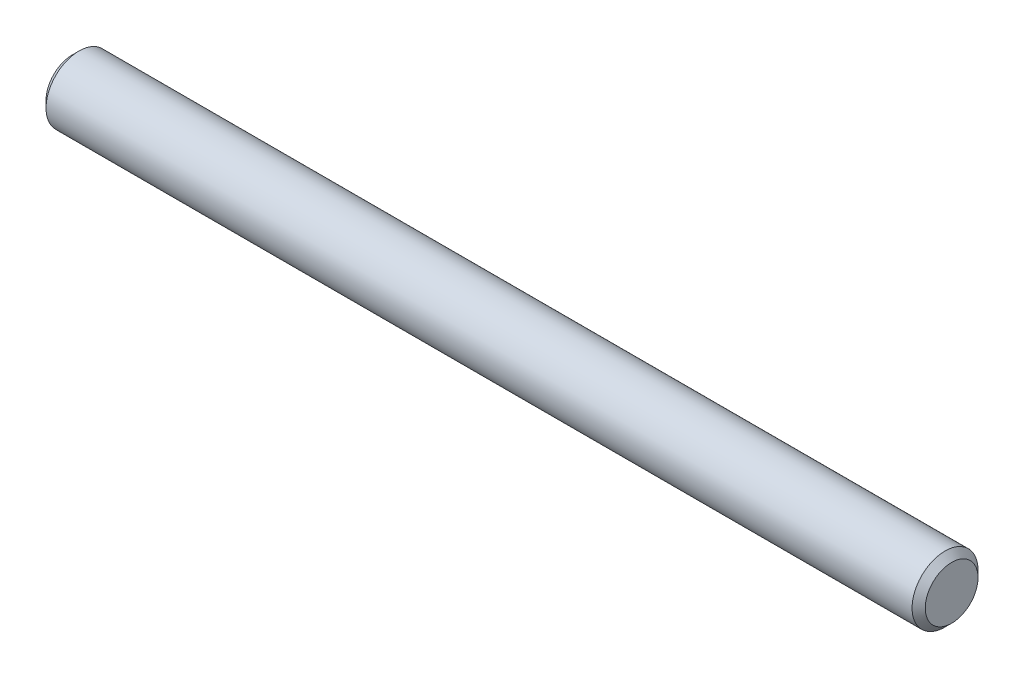
SolidWorks part; units mm, degrees
ref_plane "Front" through (0, 0, 0) normal (0, 0, 1) x (1, 0, 0)
ref_plane "Top" through (0, 0, 0) normal (0, 1, 0) x (1, 0, 0)
ref_plane "Right" through (0, 0, 0) normal (1, 0, 0) x (0, 0, -1)
sketch "Sketch1" plane through (0, 0, 0) normal (0, 0, 1) x (1, 0, 0)
  line L0 (-31.75, 0) -> (31.75, 0) construction
  line L1 (31.75, 2.3813) -> (31.75, -2.3813) construction
  line L2 (-31.75, 2.3813) -> (-31.75, -2.3813) construction
  dimension "Length" = 63.5
  dimension "Diameter" = 4.7625
sketch "Sketch2" plane through (0, 0, 0) normal (1, 0, 0) x (0, 0, -1)
  circle A0 centre (0, 0) radius 2.3813
extrude "Extrude1" add sketch "Sketch2" against normal up to vertex (31.75 mm away) and the other way up to vertex (31.75 mm away) up to point (-31.75, 2.3813, 0) other way up to point (31.75, 2.3813, 0)
chamfer "Chamfer1" distance 0.4763 angle 45 2 edges at (31.75, 0, -2.3813) (-31.75, 0, -2.3813)
equation "\"D1@Chamfer1\" = \"Diameter@Sketch1\"*.1"
